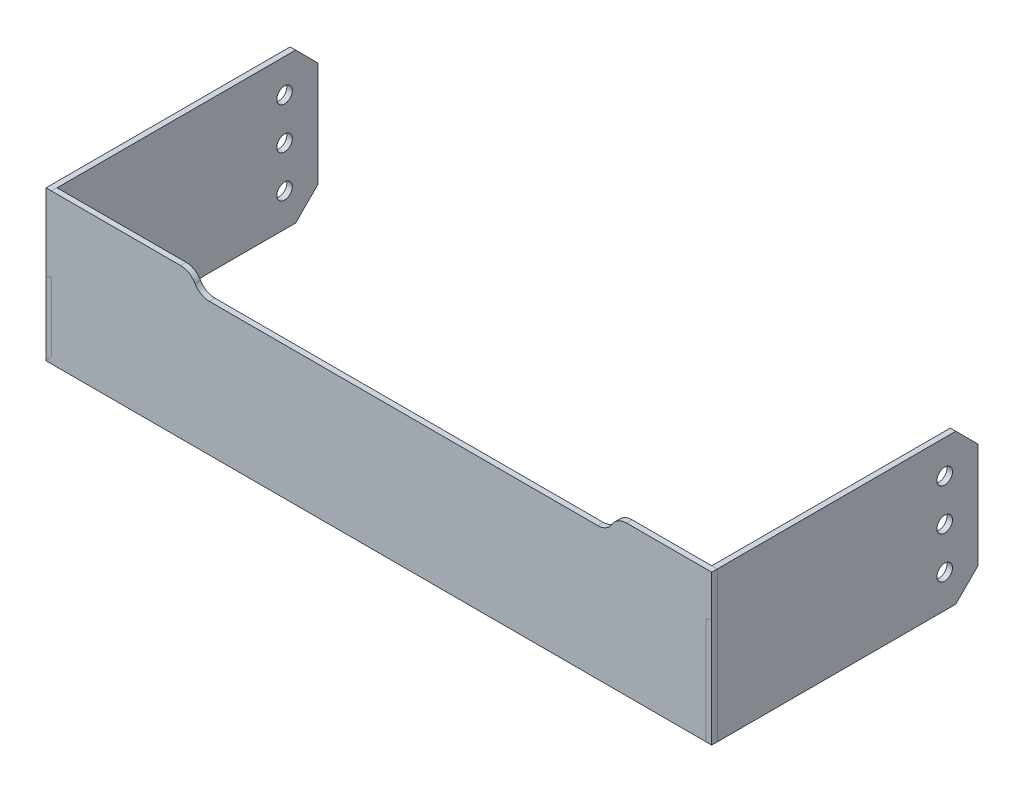
SolidWorks part; units mm, degrees
ref_plane "Front Plane" through (0, 0, 0) normal (0, 0, 1) x (1, 0, 0)
ref_plane "Top Plane" through (0, 0, 0) normal (0, 1, 0) x (1, 0, 0)
ref_plane "Right Plane" through (0, 0, 0) normal (1, 0, 0) x (0, 0, -1)
sketch "Sketch1" plane through (0, 0, 0) normal (0, 0, 1) x (1, 0, 0)
  line L0 (11.2071, -22.9067) -> (11.2071, 29.4143) construction
  line L1 (-53.2463, -5.4778) -> (66.7537, -5.4778)
  line L2 (-53.2463, -5.4778) -> (-53.2463, 21.5222)
  line L3 (-53.2463, 21.5222) -> (-26.7929, 21.5222)
  line L4 (66.7537, -5.4778) -> (66.7537, 21.5222)
  line L5 (-26.7929, 21.5222) -> (-26.7929, 18.5222)
  line L6 (-26.7929, 18.5222) -> (49.2071, 18.5222)
  line L7 (49.2071, 21.5222) -> (49.2071, 18.5222)
  line L8 (49.2071, 21.5222) -> (66.7537, 21.5222)
  point P10 (11.2071, 18.5222)
  dimension "D1" = 120
  dimension "D2" = 27
  dimension "D3" = 27
  dimension "D4" = 38
  dimension "D5" = 3
extrude "Boss-Extrude1" add sketch "Sketch1" along normal blind 1
sketch "Sketch3" plane through (66.7537, 0, 0) normal (1, 0, 0) x (0, 0, -1)
  line L1 (-1, 21.5222) -> (47, 21.5222)
  line L2 (-1, 21.5222) -> (-1, -5.4778)
  line L3 (-1, -5.4778) -> (47, -5.4778)
  line L4 (47, 21.5222) -> (47, -5.4778)
  dimension "D1" = 27
  dimension "D2" = 48
base flange "Base-Flange1" sketch "Sketch3" thickness 1 reverse thickness direction no parameters "D1"=0.7366
chamfer "Chamfer1" distance 4 angle 45 2 edges at (66.2537, -5.4778, -47) (66.2537, 21.5222, -47)
fillet "Fillet1" radius 3 2 edges at (-26.7929, 18.5222, 0.5) (49.2071, 18.5222, 0.5)
fillet "Fillet2" radius 3 2 edges at (49.2071, 21.5222, 0.5) (-26.7929, 21.5222, 0.5)
sketch "Sketch8" plane through (-53.2463, 0, 0) normal (-1, 0, 0) x (0, 0, 1)
  line L1 (1, 21.5222) -> (-47, 21.5222)
  line L2 (1, 21.5222) -> (1, -5.4778)
  line L3 (1, -5.4778) -> (-47, -5.4778)
  line L4 (-47, 21.5222) -> (-47, -5.4778)
  dimension "D1" = 48
  dimension "D2" = 27
base flange "Base-Flange2" sketch "Sketch8" thickness 1 reverse thickness direction no parameters "D1"=0.7366
chamfer "Chamfer2" distance 4 angle 45 2 edges at (-52.7463, -5.4778, -47) (-52.7463, 21.5222, -47)
sketch "Sketch11" plane through (-53.2463, 0, 0) normal (-1, 0, 0) x (0, 0, 1)
  line L0 (1, 21.5222) -> (-43, 21.5222) construction
  line L1 (-43, -5.4778) -> (1, -5.4778) construction
  line L2 (-47, 17.5222) -> (-47, -1.4778) construction
  circle A0 centre (-41, 15.5222) radius 1.4
  circle A1 centre (-41, 8.0222) radius 1.4
  circle A2 centre (-41, 0.5222) radius 1.4
  dimension "D1" = 2.8
  dimension "D2" = 2.8
  dimension "D3" = 2.8
  dimension "D4" = 6
  dimension "D5" = 6
  dimension "D6" = 15
  dimension "D7" = 7.5
  dimension "D8" = 6
  dimension "D9" = 6
extrude "Cut-Extrude1" cut sketch "Sketch11" against normal through all
sketch "Bend-Lines1" [suppressed] plane through (0, 0, 0) normal (0, 1, 0) x (1, 0, 0)
sketch "Bounding-Box1" [suppressed] plane through (0, 0, 0) normal (0, 1, 0) x (1, 0, 0)
sheet metal parameters "Sheet-Metal2" thickness 1 parameters "D1"=0.7366
flat pattern "Flat-Pattern2" [suppressed]
sketch "Bend-Lines2" plane through (0, 0, 0) normal (0, 1, 0) x (1, 0, 0)
sketch3d "Bounding-Box2" [suppressed]
  line L0 (-1, -5.4778, 0) -> (47, -5.4778, 0) construction
  line L1 (-1, 21.5222, 0) -> (47, 21.5222, 0) construction
  line L2 (-1, -5.4778, 0) -> (-1, 21.5222, 0) construction
  line L3 (47, -5.4778, 0) -> (47, 21.5222, 0) construction
sheet metal parameters "Sheet-Metal3" thickness 1 parameters "D1"=0.7366
flat pattern "Flat-Pattern3"
sketch "Bend-Lines3" plane through (0, 0, 0) normal (0, 1, 0) x (1, 0, 0)
sketch3d "Bounding-Box3" [suppressed]
  line L0 (-1, -5.4778, 0) -> (47, -5.4778, 0) construction
  line L1 (-1, 21.5222, 0) -> (47, 21.5222, 0) construction
  line L2 (-1, -5.4778, 0) -> (-1, 21.5222, 0) construction
  line L3 (47, -5.4778, 0) -> (47, 21.5222, 0) construction
sheet metal parameters "Sheet-Metal4" thickness 1 parameters "D1"=0.7366
flat pattern "Flat-Pattern2"
sketch "Bend-Lines2" plane through (0, 0, 0) normal (0, 1, 0) x (1, 0, 0)
sketch3d "Bounding-Box2" [suppressed]
  line L0 (-1, -5.4778, 0) -> (47, -5.4778, 0) construction
  line L1 (-1, 21.5222, 0) -> (47, 21.5222, 0) construction
  line L2 (-1, -5.4778, 0) -> (-1, 21.5222, 0) construction
  line L3 (47, -5.4778, 0) -> (47, 21.5222, 0) construction
sheet metal parameters "Sheet-Metal5" thickness 1 parameters "D1"=0.7366
flat pattern "Flat-Pattern3"
sketch "Bend-Lines3" plane through (0, 0, 0) normal (0, 1, 0) x (1, 0, 0)
sketch3d "Bounding-Box3" [suppressed]
  line L0 (-1, -5.4778, 0) -> (47, -5.4778, 0) construction
  line L1 (-1, 21.5222, 0) -> (47, 21.5222, 0) construction
  line L2 (-1, -5.4778, 0) -> (-1, 21.5222, 0) construction
  line L3 (47, -5.4778, 0) -> (47, 21.5222, 0) construction
